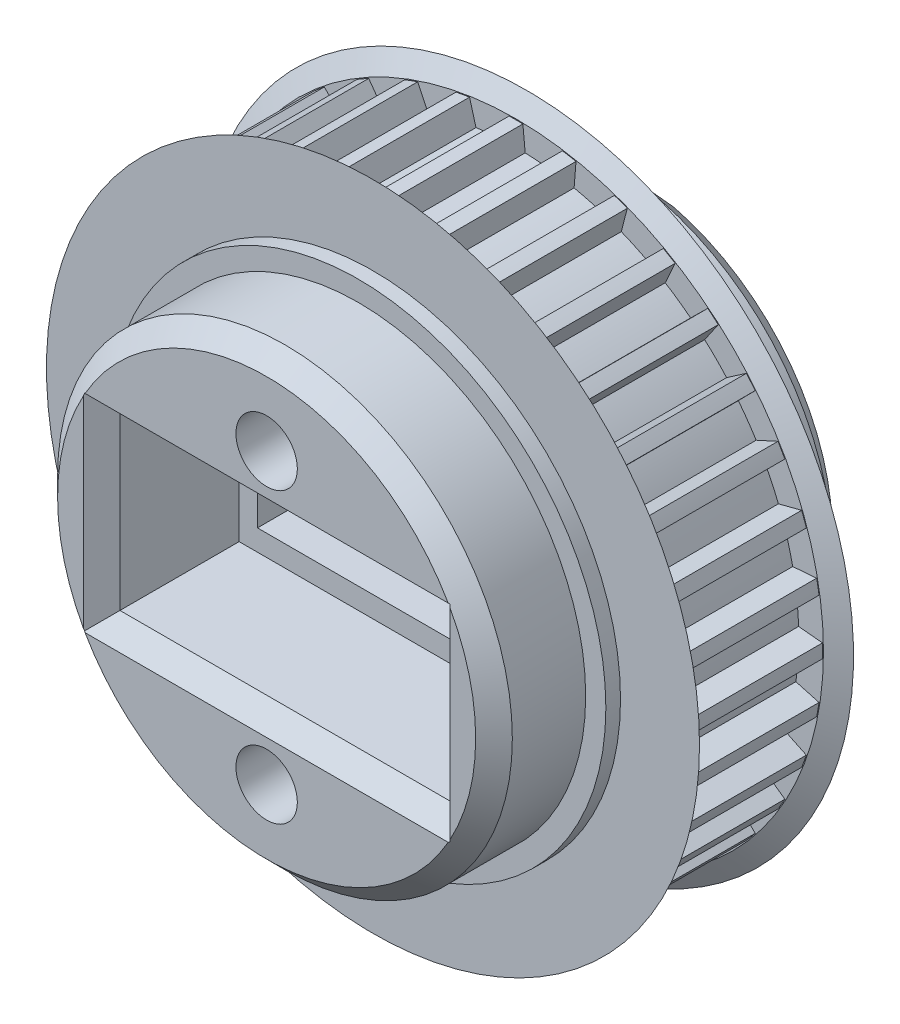
SolidWorks part; units mm, degrees
material "ABS"
ref_plane "Alzado" through (0, 0, 0) normal (0, 0, 1) x (1, 0, 0)
ref_plane "Planta" through (0, 0, 0) normal (0, 1, 0) x (1, 0, 0)
ref_plane "Vista lateral" through (0, 0, 0) normal (1, 0, 0) x (0, 0, -1)
sketch "Croquis1" plane through (0, 0, 0) normal (0, 0, 1) x (1, 0, 0)
  line L0 (0, 0) -> (0, 14.5885) construction
  line L1 (-0.375, 16.7142) -> (-0.5, 15.4103)
  line L2 (0.375, 16.7142) -> (0.5, 15.4103)
  line L3 (3.2717, 16.3952) -> (3.1684, 15.0894)
  line L4 (2.5331, 16.5254) -> (2.1836, 15.263)
  line L5 (6.069, 15.578) -> (5.7405, 14.3099)
  line L6 (5.3642, 15.8345) -> (4.8008, 14.652)
  line L7 (8.6819, 14.2874) -> (8.1382, 13.0957)
  line L8 (8.0323, 14.6624) -> (7.2721, 13.5957)
  line L9 (11.031, 12.5628) -> (10.2886, 11.4836)
  line L10 (10.4564, 13.0449) -> (9.5225, 12.1264)
  line L11 (13.0449, 10.4564) -> (12.1264, 9.5225)
  line L12 (12.5628, 11.031) -> (11.4836, 10.2886)
  line L13 (14.6624, 8.0323) -> (13.5957, 7.2721)
  line L14 (14.2874, 8.6819) -> (13.0957, 8.1382)
  line L15 (15.8345, 5.3642) -> (14.652, 4.8008)
  line L16 (15.578, 6.069) -> (14.3099, 5.7405)
  line L17 (16.5254, 2.5331) -> (15.263, 2.1836)
  line L18 (16.3952, 3.2717) -> (15.0894, 3.1684)
  line L19 (16.7142, -0.375) -> (15.4103, -0.5)
  line L20 (16.7142, 0.375) -> (15.4103, 0.5)
  line L21 (16.3952, -3.2717) -> (15.0894, -3.1684)
  line L22 (16.5254, -2.5331) -> (15.263, -2.1836)
  line L23 (15.578, -6.069) -> (14.3099, -5.7405)
  line L24 (15.8345, -5.3642) -> (14.652, -4.8008)
  line L25 (14.2874, -8.6819) -> (13.0957, -8.1382)
  line L26 (14.6624, -8.0323) -> (13.5957, -7.2721)
  line L27 (12.5628, -11.031) -> (11.4836, -10.2886)
  line L28 (13.0449, -10.4564) -> (12.1264, -9.5225)
  line L29 (10.4564, -13.0449) -> (9.5225, -12.1264)
  line L30 (11.031, -12.5628) -> (10.2886, -11.4836)
  line L31 (8.0323, -14.6624) -> (7.2721, -13.5957)
  line L32 (8.6819, -14.2874) -> (8.1382, -13.0957)
  line L33 (5.3642, -15.8345) -> (4.8008, -14.652)
  line L34 (6.069, -15.578) -> (5.7405, -14.3099)
  line L35 (2.5331, -16.5254) -> (2.1836, -15.263)
  line L36 (3.2717, -16.3952) -> (3.1684, -15.0894)
  line L37 (-0.375, -16.7142) -> (-0.5, -15.4103)
  line L38 (0.375, -16.7142) -> (0.5, -15.4103)
  line L39 (-3.2717, -16.3952) -> (-3.1684, -15.0894)
  line L40 (-2.5331, -16.5254) -> (-2.1836, -15.263)
  line L41 (-6.069, -15.578) -> (-5.7405, -14.3099)
  line L42 (-5.3642, -15.8345) -> (-4.8008, -14.652)
  line L43 (-8.6819, -14.2874) -> (-8.1382, -13.0957)
  line L44 (-8.0323, -14.6624) -> (-7.2721, -13.5957)
  line L45 (-11.031, -12.5628) -> (-10.2886, -11.4836)
  line L46 (-10.4564, -13.0449) -> (-9.5225, -12.1264)
  line L47 (-13.0449, -10.4564) -> (-12.1264, -9.5225)
  line L48 (-12.5628, -11.031) -> (-11.4836, -10.2886)
  line L49 (-14.6624, -8.0323) -> (-13.5957, -7.2721)
  line L50 (-14.2874, -8.6819) -> (-13.0957, -8.1382)
  line L51 (-15.8345, -5.3642) -> (-14.652, -4.8008)
  line L52 (-15.578, -6.069) -> (-14.3099, -5.7405)
  line L53 (-16.5254, -2.5331) -> (-15.263, -2.1836)
  line L54 (-16.3952, -3.2717) -> (-15.0894, -3.1684)
  line L55 (-16.7142, 0.375) -> (-15.4103, 0.5)
  line L56 (-16.7142, -0.375) -> (-15.4103, -0.5)
  line L57 (-16.3952, 3.2717) -> (-15.0894, 3.1684)
  line L58 (-16.5254, 2.5331) -> (-15.263, 2.1836)
  line L59 (-15.578, 6.069) -> (-14.3099, 5.7405)
  line L60 (-15.8345, 5.3642) -> (-14.652, 4.8008)
  line L61 (-14.2874, 8.6819) -> (-13.0957, 8.1382)
  line L62 (-14.6624, 8.0323) -> (-13.5957, 7.2721)
  line L63 (-12.5628, 11.031) -> (-11.4836, 10.2886)
  line L64 (-13.0449, 10.4564) -> (-12.1264, 9.5225)
  line L65 (-10.4564, 13.0449) -> (-9.5225, 12.1264)
  line L66 (-11.031, 12.5628) -> (-10.2886, 11.4836)
  line L67 (-8.0323, 14.6624) -> (-7.2721, 13.5957)
  line L68 (-8.6819, 14.2874) -> (-8.1382, 13.0957)
  line L69 (-5.3642, 15.8345) -> (-4.8008, 14.652)
  line L70 (-6.069, 15.578) -> (-5.7405, 14.3099)
  line L71 (-2.5331, 16.5254) -> (-2.1836, 15.263)
  line L72 (-3.2717, 16.3952) -> (-3.1684, 15.0894)
  arc A0 (-10.4564, 13.0449) -> (-11.031, 12.5628) centre (0, 0) ccw
  arc A1 (2.1836, 15.263) -> (0.5, 15.4103) centre (0, 0) ccw
  arc A2 (-12.5628, 11.031) -> (-13.0449, 10.4564) centre (0, 0) ccw
  arc A3 (-14.2874, 8.6819) -> (-14.6624, 8.0323) centre (0, 0) ccw
  arc A4 (-15.578, 6.069) -> (-15.8345, 5.3642) centre (0, 0) ccw
  arc A5 (-16.3952, 3.2717) -> (-16.5254, 2.5331) centre (0, 0) ccw
  arc A6 (-16.7142, 0.375) -> (-16.7142, -0.375) centre (0, 0) ccw
  arc A7 (-16.5254, -2.5331) -> (-16.3952, -3.2717) centre (0, 0) ccw
  arc A8 (-15.8345, -5.3642) -> (-15.578, -6.069) centre (0, 0) ccw
  arc A9 (-14.6624, -8.0323) -> (-14.2874, -8.6819) centre (0, 0) ccw
  arc A10 (-13.0449, -10.4564) -> (-12.5628, -11.031) centre (0, 0) ccw
  arc A11 (3.2717, 16.3952) -> (2.5331, 16.5254) centre (0, 0) ccw
  arc A12 (0.375, 16.7142) -> (-0.375, 16.7142) centre (0, 0) ccw
  arc A13 (-5.3642, 15.8345) -> (-6.069, 15.578) centre (0, 0) ccw
  arc A14 (-8.0323, 14.6624) -> (-8.6819, 14.2874) centre (0, 0) ccw
  arc A15 (-2.5331, 16.5254) -> (-3.2717, 16.3952) centre (0, 0) ccw
  arc A16 (6.069, 15.578) -> (5.3642, 15.8345) centre (0, 0) ccw
  arc A17 (8.6819, 14.2874) -> (8.0323, 14.6624) centre (0, 0) ccw
  arc A18 (11.031, 12.5628) -> (10.4564, 13.0449) centre (0, 0) ccw
  arc A19 (13.0449, 10.4564) -> (12.5628, 11.031) centre (0, 0) ccw
  arc A20 (14.6624, 8.0323) -> (14.2874, 8.6819) centre (0, 0) ccw
  arc A21 (15.8345, 5.3642) -> (15.578, 6.069) centre (0, 0) ccw
  arc A22 (16.5254, 2.5331) -> (16.3952, 3.2717) centre (0, 0) ccw
  arc A23 (16.7142, -0.375) -> (16.7142, 0.375) centre (0, 0) ccw
  arc A24 (16.3952, -3.2717) -> (16.5254, -2.5331) centre (0, 0) ccw
  arc A25 (15.578, -6.069) -> (15.8345, -5.3642) centre (0, 0) ccw
  arc A26 (8.0323, -14.6624) -> (8.6819, -14.2874) centre (0, 0) ccw
  arc A27 (5.3642, -15.8345) -> (6.069, -15.578) centre (0, 0) ccw
  arc A28 (2.5331, -16.5254) -> (3.2717, -16.3952) centre (0, 0) ccw
  arc A29 (-3.2717, -16.3952) -> (-2.5331, -16.5254) centre (0, 0) ccw
  arc A30 (-6.069, -15.578) -> (-5.3642, -15.8345) centre (0, 0) ccw
  arc A31 (-8.6819, -14.2874) -> (-8.0323, -14.6624) centre (0, 0) ccw
  arc A32 (-11.031, -12.5628) -> (-10.4564, -13.0449) centre (0, 0) ccw
  arc A33 (10.4564, -13.0449) -> (11.031, -12.5628) centre (0, 0) ccw
  arc A34 (12.5628, -11.031) -> (13.0449, -10.4564) centre (0, 0) ccw
  arc A35 (14.2874, -8.6819) -> (14.6624, -8.0323) centre (0, 0) ccw
  arc A36 (4.8008, 14.652) -> (3.1684, 15.0894) centre (0, 0) ccw
  arc A37 (7.2721, 13.5957) -> (5.7405, 14.3099) centre (0, 0) ccw
  arc A38 (-3.1684, 15.0894) -> (-4.8008, 14.652) centre (0, 0) ccw
  arc A39 (-0.5, 15.4103) -> (-2.1836, 15.263) centre (0, 0) ccw
  arc A40 (-5.7405, 14.3099) -> (-7.2721, 13.5957) centre (0, 0) ccw
  arc A41 (-8.1382, 13.0957) -> (-9.5225, 12.1264) centre (0, 0) ccw
  arc A42 (-10.2886, 11.4836) -> (-11.4836, 10.2886) centre (0, 0) ccw
  arc A43 (9.5225, 12.1264) -> (8.1382, 13.0957) centre (0, 0) ccw
  arc A44 (11.4836, 10.2886) -> (10.2886, 11.4836) centre (0, 0) ccw
  arc A45 (13.0957, 8.1382) -> (12.1264, 9.5225) centre (0, 0) ccw
  arc A46 (14.3099, 5.7405) -> (13.5957, 7.2721) centre (0, 0) ccw
  arc A47 (15.0894, 3.1684) -> (14.652, 4.8008) centre (0, 0) ccw
  arc A48 (15.4103, 0.5) -> (15.263, 2.1836) centre (0, 0) ccw
  arc A49 (15.263, -2.1836) -> (15.4103, -0.5) centre (0, 0) ccw
  arc A50 (14.652, -4.8008) -> (15.0894, -3.1684) centre (0, 0) ccw
  arc A51 (13.5957, -7.2721) -> (14.3099, -5.7405) centre (0, 0) ccw
  arc A52 (12.1264, -9.5225) -> (13.0957, -8.1382) centre (0, 0) ccw
  arc A53 (10.2886, -11.4836) -> (11.4836, -10.2886) centre (0, 0) ccw
  arc A54 (8.1382, -13.0957) -> (9.5225, -12.1264) centre (0, 0) ccw
  arc A55 (5.7405, -14.3099) -> (7.2721, -13.5957) centre (0, 0) ccw
  arc A56 (3.1684, -15.0894) -> (4.8008, -14.652) centre (0, 0) ccw
  arc A57 (0.5, -15.4103) -> (2.1836, -15.263) centre (0, 0) ccw
  arc A58 (-2.1836, -15.263) -> (-0.5, -15.4103) centre (0, 0) ccw
  arc A59 (-4.8008, -14.652) -> (-3.1684, -15.0894) centre (0, 0) ccw
  arc A60 (-7.2721, -13.5957) -> (-5.7405, -14.3099) centre (0, 0) ccw
  arc A61 (-9.5225, -12.1264) -> (-8.1382, -13.0957) centre (0, 0) ccw
  arc A62 (-11.4836, -10.2886) -> (-10.2886, -11.4836) centre (0, 0) ccw
  arc A63 (-13.0957, -8.1382) -> (-12.1264, -9.5225) centre (0, 0) ccw
  arc A64 (-14.3099, -5.7405) -> (-13.5957, -7.2721) centre (0, 0) ccw
  arc A65 (-15.0894, -3.1684) -> (-14.652, -4.8008) centre (0, 0) ccw
  arc A66 (-15.4103, -0.5) -> (-15.263, -2.1836) centre (0, 0) ccw
  arc A67 (-15.263, 2.1836) -> (-15.4103, 0.5) centre (0, 0) ccw
  arc A68 (-14.652, 4.8008) -> (-15.0894, 3.1684) centre (0, 0) ccw
  arc A69 (-13.5957, 7.2721) -> (-14.3099, 5.7405) centre (0, 0) ccw
  arc A70 (-12.1264, 9.5225) -> (-13.0957, 8.1382) centre (0, 0) ccw
  arc A71 (-0.375, -16.7142) -> (0.375, -16.7142) centre (0, 0) ccw
  circle A72 centre (0, 0) radius 2
  point P151 (0, 0)
  dimension "D1" = 1.3
  dimension "D6" = 4
  dimension "D2" = 1
  dimension "D3" = 0.75
  dimension "D5" = 1.69
  dimension "D4" = 36
extrude "Saliente-Extruir1" add sketch "Croquis1" along normal blind 7.2
sketch "Croquis2" plane through (0, 0, 7.2) normal (0, 0, 1) x (1, 0, 0)
  circle A0 centre (0, 0) radius 18.5
  circle A1 centre (0, 0) radius 2
  circle A2 centre (0, 0) radius 2 construction
  dimension "D1" = 37
extrude "Saliente-Extruir2" add sketch "Croquis2" along normal blind 0.6
sketch "Croquis3" plane through (0, 0, 7.8) normal (0, 0, 1) x (1, 0, 0)
  circle A0 centre (0, 0) radius 2
  circle A1 centre (0, 0) radius 12.4
  circle A3 centre (0, 0) radius 2 construction
  dimension "D1" = 24.8
sketch "Croquis4" plane through (0, 0, 0) normal (0, 0, -1) x (-1, 0, 0)
  circle A0 centre (0, 0) radius 2
  circle A1 centre (0, 0) radius 12.45
  circle A2 centre (0, 0) radius 2 construction
  dimension "D1" = 24.9
extrude "Saliente-Extruir4" add sketch "Croquis4" along normal blind 5.8
sketch "Croquis6" plane through (0, 0, 0) normal (0, 0, -1) x (-1, 0, 0)
  circle A0 centre (0, 0) radius 18.5
  circle A1 centre (0, 0) radius 2
  circle A2 centre (0, 0) radius 2 construction
  dimension "D1" = 37
extrude "Saliente-Extruir6" add sketch "Croquis6" along normal blind 0.6
sketch "Croquis5" plane through (0, 0, -0.6) normal (0, 0, -1) x (-1, 0, 0)
  circle A0 centre (0, 0) radius 2
  circle A1 centre (0, 0) radius 13.5
  circle A2 centre (0, 0) radius 2 construction
  dimension "D1" = 27
extrude "Saliente-Extruir5" add sketch "Croquis5" along normal blind 0.6
chamfer "Chaflán2" distance 1 angle 60 2 edges at (-18.5, 0, 0) (18.5, 0, 7.2)
extrude "Saliente-Extruir7" add sketch "Croquis3" along normal blind 5.8
chamfer "Chaflán4" distance 1 angle 45 2 edges at (-12.45, 0, -5.8) (12.4, 0, 13.6)
sketch "Croquis7" plane through (0, 0, 7.8) normal (0, 0, 1) x (1, 0, 0)
  circle A0 centre (0, 0) radius 2
  circle A1 centre (0, 0) radius 13.5
  circle A2 centre (0, 0) radius 2 construction
  dimension "D1" = 27
extrude "Saliente-Extruir8" add sketch "Croquis7" along normal blind 0.8
sketch "Croquis8" plane through (0, 0, 0) normal (0, 0, 1) x (1, 0, 0)
  line L0 (0, 0) -> (6.706, 0) construction
  line L1 (-8, 3.5) -> (8, 3.5)
  line L2 (-8, 3.5) -> (-8, -3.5)
  line L3 (-8, -3.5) -> (8, -3.5)
  line L4 (8, 3.5) -> (8, -3.5)
  line L5 (-8, 3.5) -> (8, -3.5) construction
  line L6 (-8, -3.5) -> (8, 3.5) construction
  circle A0 centre (0, 7.8756) radius 1.675
  circle A1 centre (0, -7.8756) radius 1.675
  point P0 (0, 0)
  dimension "D1" = 3.35
  dimension "D2" = 7
  dimension "D3" = 16
extrude "Cortar-Extruir1" cut sketch "Croquis8" against normal through all both and the other way through all
sketch "Croquis9" plane through (0, 0, -5.8) normal (0, 0, -1) x (-1, 0, 0)
  line L1 (2.3383, 3.8256) -> (4.6765, 7.8756)
  line L2 (4.6765, 7.8756) -> (2.3383, 11.9256)
  line L3 (2.3383, 11.9256) -> (-2.3383, 11.9256)
  line L4 (-2.3383, 11.9256) -> (-4.6765, 7.8756)
  line L5 (-4.6765, 7.8756) -> (-2.3383, 3.8256)
  line L6 (-2.3383, 3.8256) -> (2.3383, 3.8256)
  line L7 (2.3383, -11.9256) -> (4.6765, -7.8756)
  line L8 (4.6765, -7.8756) -> (2.3383, -3.8256)
  line L9 (2.3383, -3.8256) -> (-2.3383, -3.8256)
  line L10 (-2.3383, -3.8256) -> (-4.6765, -7.8756)
  line L11 (-4.6765, -7.8756) -> (-2.3383, -11.9256)
  line L12 (-2.3383, -11.9256) -> (2.3383, -11.9256)
  circle A0 centre (0, 7.8756) radius 4.05 construction
  circle A1 centre (0, -7.8756) radius 4.05 construction
  dimension "D1" = 8.1
extrude "Cortar-Extruir2" cut sketch "Croquis9" against normal blind 5.5
fillet "Redondeo1" radius 2.5 12 edges at (3.5074, -9.9006, -0.3) (3.5074, -5.8506, -0.3) (0, -3.8256, -0.3) (-3.5074, -5.8506, -0.3) (0, -11.9256, -0.3) (-3.5074, -9.9006, -0.3) (-3.5074, 5.8506, -0.3) (-3.5074, 9.9006, -0.3) (0, 11.9256, -0.3) (3.5074, 9.9006, -0.3) (3.5074, 5.8506, -0.3) (0, 3.8256, -0.3)
sketch "Croquis10" plane through (0, 0, 13.6) normal (0, 0, 1) x (1, 0, 0)
  line L1 (9, 4.65) -> (-9, 4.65)
  line L2 (9, 4.65) -> (9, -4.65)
  line L3 (9, -4.65) -> (-9, -4.65)
  line L4 (-9, 4.65) -> (-9, -4.65)
  line L5 (9, 4.65) -> (-9, -4.65) construction
  line L6 (9, -4.65) -> (-9, 4.65) construction
  point P0 (0, 0)
  dimension "D1" = 9.3
  dimension "D2" = 18
extrude "Cortar-Extruir3" cut sketch "Croquis10" against normal blind 7.5
chamfer "Chaflán5" distance 1 angle 45 8 edges at (-8, 0, -5.8) (0, 3.5, -5.8) (8, 0, -5.8) (0, -3.5, -5.8) (9, 0, 13.6) (0, 4.65, 13.6) (-9, 0, 13.6) (0, -4.65, 13.6)
